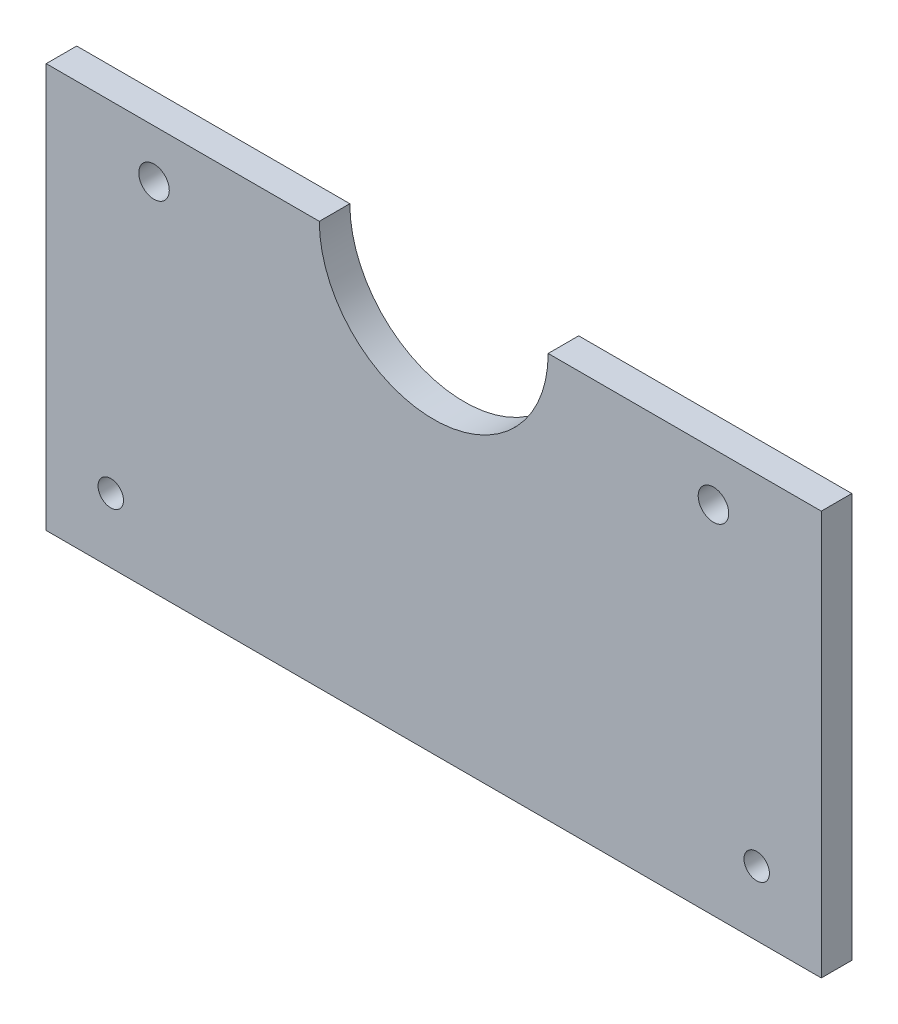
SolidWorks part; units mm, degrees
ref_plane "Front Plane" through (0, 0, 0) normal (0, 0, 1) x (1, 0, 0)
ref_plane "Top Plane" through (0, 0, 0) normal (0, 1, 0) x (1, 0, 0)
ref_plane "Right Plane" through (0, 0, 0) normal (1, 0, 0) x (0, 0, -1)
sketch "Sketch2" plane through (0, 0, 0) normal (0, 0, 1) x (1, 0, 0)
  line L0 (-55, 70) -> (55, 70) construction
  line L1 (-76.2, 0) -> (76.2, 0)
  line L2 (-76.2, 0) -> (-76.2, 79.5)
  line L3 (-76.2, 79.5) -> (76.2, 79.5) construction
  line L4 (76.2, 0) -> (76.2, 79.5)
  line L5 (0, 70) -> (0, 0) construction
  line L6 (0, 70) -> (0, 79.5) construction
  line L7 (0, 79.5) -> (-22.5, 79.5) construction
  line L8 (-22.5, 79.5) -> (-76.2, 79.5)
  line L9 (22.5, 79.5) -> (76.2, 79.5)
  circle A0 centre (-55, 70) radius 3
  circle A1 centre (55, 70) radius 3
  circle A2 centre (-55, 70) radius 16 construction
  circle A3 centre (55, 70) radius 16 construction
  arc A4 (-22.5, 79.5) -> (22.5, 79.5) centre (0, 79.5) ccw
  point P6 (0, 0)
  dimension "D1" = 6
  dimension "D2" = 32
  dimension "D5" = 45
  dimension "D3" = 110
  dimension "D4" = 9.5
  dimension "D6" = 152.4
  dimension "D7" = 70
extrude "Boss-Extrude1" add sketch "Sketch2" along normal mid plane 6
sketch "Sketch3" plane through (0, 0, 3) normal (0, 0, 1) x (1, 0, 0)
  line L1 (-76.2, 0) -> (-63.5, 0) construction
  line L2 (-76.2, 0) -> (-76.2, 12.7) construction
  line L3 (-76.2, 12.7) -> (-63.5, 12.7) construction
  line L4 (-63.5, 0) -> (-63.5, 12.7) construction
  line L5 (76.2, 0) -> (63.5, 0) construction
  line L6 (76.2, 0) -> (76.2, 12.7) construction
  line L7 (76.2, 12.7) -> (63.5, 12.7) construction
  line L8 (63.5, 0) -> (63.5, 12.7) construction
  circle A0 centre (-63.5, 12.7) radius 2.5
  circle A1 centre (63.5, 12.7) radius 2.5
  dimension "D1" = 12.7
  dimension "D2" = 5
  dimension "D3" = 12.7
extrude "Cut-Extrude1" cut sketch "Sketch3" against normal blind 6
